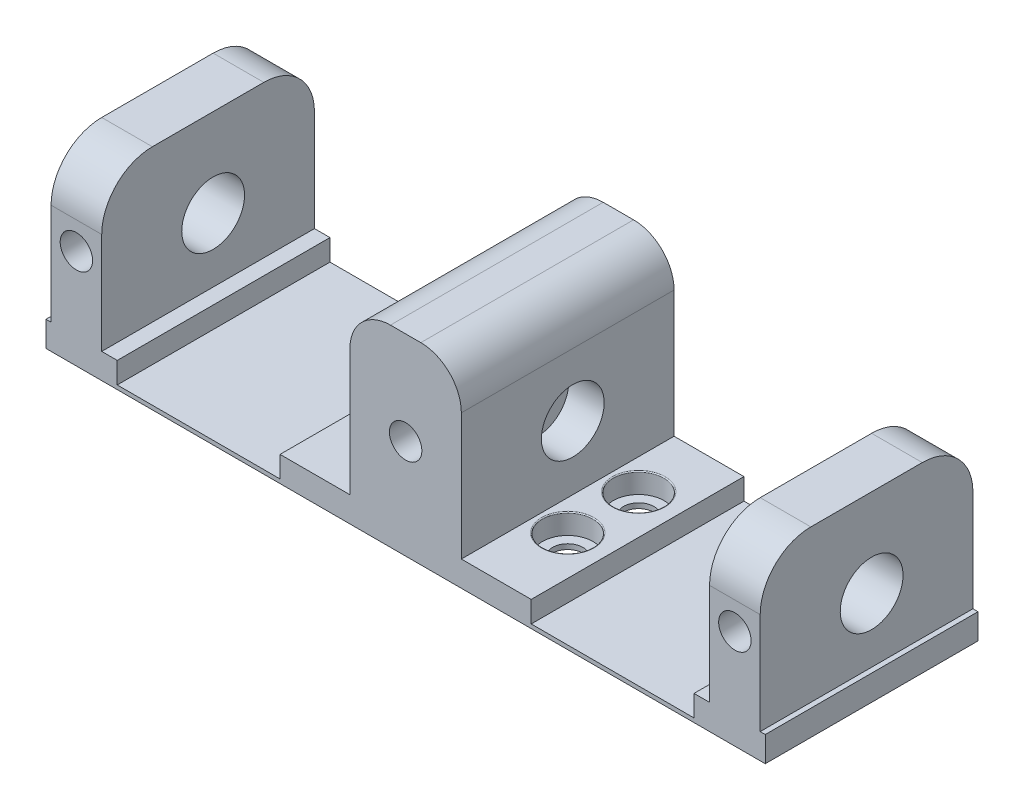
SolidWorks part; units mm, degrees
ref_plane "Alzado" through (0, 0, 0) normal (0, 0, 1) x (1, 0, 0)
ref_plane "Planta" through (0, 0, 0) normal (0, 1, 0) x (1, 0, 0)
ref_plane "Vista lateral" through (0, 0, 0) normal (1, 0, 0) x (0, 0, -1)
sketch "Croquis1" plane through (0, 0, 0) normal (0, 0, 1) x (1, 0, 0)
  line L0 (0, 9.5) -> (0, -9.5) construction
  line L1 (-1.5, 9.5) -> (1.5, 9.5)
  line L2 (-5.5, 5.5) -> (-5.5, -7)
  line L3 (-5.5, -9.5) -> (5.5, -9.5)
  line L4 (5.5, 5.5) -> (5.5, -7)
  line L5 (-5.5, 9.5) -> (5.5, -9.5) construction
  line L6 (-5.5, -9.5) -> (5.5, 9.5) construction
  line L7 (-5.5, -9.5) -> (-11.5, -9.5)
  line L9 (-5.5, -7) -> (-11.5, -7)
  line L10 (-11.5, -9.5) -> (-11.5, -7)
  line L11 (5.5, -7) -> (11.5, -7)
  line L12 (11.5, -9.5) -> (11.5, -7)
  line L13 (5.5, -9.5) -> (11.5, -9.5)
  arc A0 (5.5, 5.5) -> (1.5, 9.5) centre (1.5, 5.5) ccw
  arc A1 (-5.5, 5.5) -> (-1.5, 9.5) centre (-1.5, 5.5) cw
  point P0 (0, 0)
  dimension "D1" = 4
  dimension "D2" = 6
  dimension "D3" = 2.5
  dimension "D4" = 11
  dimension "D5" = 15
extrude "Saliente-Extruir1" add sketch "Croquis1" against normal blind 11 and the other way blind 10
sketch "Croquis2" plane through (5.5, 0, 0) normal (1, 0, 0) x (0, 0, -1)
  line L0 (0.5, 9.5) -> (0.5, -7) construction
  line L1 (11, 9.5) -> (-10, 9.5) construction
  line L2 (11, -7) -> (-10, -7) construction
  line L3 (11, -9.5) -> (-10, -9.5) construction
  line L4 (-10, -7) -> (-10, 5.5) construction
  circle A0 centre (1, -0.68) radius 3.1
  point P10 (0, 0)
  dimension "D2" = 6.2
  dimension "D1" = 8.82
  dimension "D3" = 11
extrude "Cortar-Extruir1" cut sketch "Croquis2" against normal blind 3.5
sketch "Croquis3" plane through (-5.5, 0, 0) normal (-1, 0, 0) x (0, 0, 1)
  line L0 (-0.5, 9.5) -> (-0.5, -7) construction
  line L1 (-11, 9.5) -> (10, 9.5) construction
  line L2 (-11, -7) -> (10, -7) construction
  line L3 (-11, -9.5) -> (10, -9.5) construction
  line L4 (10, 5.5) -> (10, -7) construction
  circle A0 centre (-1, -0.68) radius 3.1
  point P10 (0, 0)
  dimension "D2" = 6.2
  dimension "D1" = 8.82
  dimension "D3" = 11
extrude "Cortar-Extruir2" cut sketch "Croquis3" against normal blind 3.5
sketch "Croquis4" plane through (0, -7, 0) normal (0, 1, 0) x (1, 0, 0)
  line L0 (0, 11) -> (0, 0) construction
  line L1 (1.5, 11) -> (-1.5, 11) construction
  line L2 (-8.5, 11) -> (-8.5, -10) construction
  line L3 (-5.5, 11) -> (-11.5, 11) construction
  line L4 (-5.5, -10) -> (-11.5, -10) construction
  line L7 (-11.5, 11) -> (-11.5, -10) construction
  line L8 (-11.5, 0.5) -> (-8.5, 0.5) construction
  circle A0 centre (-8.5, 4.5) radius 2.5
  circle A1 centre (-8.5, -2.5) radius 2.5
  circle A2 centre (8.5, -2.5) radius 2.5
  circle A3 centre (8.5, 4.5) radius 2.5
  dimension "D1" = 5
  dimension "D2" = 7
  dimension "D3" = 6.5
extrude "Cortar-Extruir3" cut sketch "Croquis4" against normal blind 2
fillet "Redondeo1" radius 0.1 4 edges at (11, -7, 2.5) (11, -7, -4.5) (-11, -7, 2.5) (-11, -7, -4.5)
sketch "Croquis5" plane through (0, -7, 0) normal (0, 1, 0) x (1, 0, 0)
  line L0 (-8.5, 11) -> (-8.5, -10) construction
  line L1 (-5.5, 11) -> (-11.5, 11) construction
  line L2 (-5.5, -10) -> (-11.5, -10) construction
  line L3 (0, 11) -> (0, -10) construction
  line L4 (1.5, 11) -> (-1.5, 11) construction
  line L5 (1.5, -10) -> (-1.5, -10) construction
  circle A0 centre (-8.5, 4.5) radius 1.5
  circle A1 centre (-8.5, -2.5) radius 1.5
  circle A2 centre (-8.5, 4.5) radius 2.6 construction
  circle A3 centre (8.5, -2.5) radius 1.5
  circle A4 centre (8.5, 4.5) radius 1.5
  dimension "D1" = 3
extrude "Cortar-Extruir4" cut sketch "Croquis5" against normal through all
sketch "Croquis6" plane through (-11.5, 0, 0) normal (-1, 0, 0) x (0, 0, 1)
  line L1 (-11, -7) -> (10, -7)
  line L2 (-11, -7) -> (-11, -9.5)
  line L3 (-11, -9.5) -> (10, -9.5)
  line L4 (10, -7) -> (10, -9.5)
extrude "Saliente-Extruir2" add sketch "Croquis6" along normal blind 24
sketch "Croquis7" plane through (11.5, 0, 0) normal (1, 0, 0) x (0, 0, -1)
  line L1 (-10, -7) -> (11, -7)
  line L2 (-10, -7) -> (-10, -9.5)
  line L3 (-10, -9.5) -> (11, -9.5)
  line L4 (11, -7) -> (11, -9.5)
extrude "Saliente-Extruir3" add sketch "Croquis7" along normal blind 24
sketch "Croquis8" plane through (0, -7, 0) normal (0, 1, 0) x (1, 0, 0)
  line L0 (-5.5, 11) -> (-35.5, 11) construction
  line L1 (-35, 11) -> (-30, 11)
  line L2 (-35, 11) -> (-35, -10)
  line L3 (-35, -10) -> (-30, -10)
  line L4 (-30, 11) -> (-30, -10)
  line L5 (-5.5, -10) -> (-35.5, -10) construction
  line L6 (0, 11) -> (0, 0) construction
  line L7 (1.5, 11) -> (-1.5, 11) construction
  line L8 (35, -10) -> (30, -10)
  line L9 (30, 11) -> (30, -10)
  line L10 (35, 11) -> (30, 11)
  line L11 (35, 11) -> (35, -10)
  line L12 (-35.5, -10) -> (-35.5, 11) construction
  dimension "D1" = 5
  dimension "D2" = 0.5
extrude "Saliente-Extruir4" add sketch "Croquis8" along normal blind 15
fillet "Redondeo4" radius 5 2 edges at (-32.5, 8, -11) (-32.5, 8, 10)
fillet "Redondeo5" radius 5 2 edges at (32.5, 8, -11) (32.5, 8, 10)
ref_plane "Plano12" through (0, 0, -0.5) normal (0, 0, 1) x (1, 0, 0)
sketch "Croquis34" plane through (0, 0, 10) normal (0, 0, 1) x (1, 0, 0)
  line L0 (-30, -7) -> (-28.4683, -7)
  line L1 (-5.5, -7) -> (-30, -7) construction
  line L2 (-28.4683, -7) -> (-28.4683, -9.1)
  line L3 (-28.4683, -9.1) -> (-12.3966, -9.1)
  line L4 (-12.3966, -9.1) -> (-12.3966, -7)
  line L5 (-28.4683, -7) -> (-12.3966, -7)
  line L6 (0, -9.5) -> (0, 0) construction
  line L8 (28.4683, -7) -> (28.4683, -9.1)
  line L9 (28.4683, -9.1) -> (12.3966, -9.1)
  line L10 (12.3966, -9.1) -> (12.3966, -7)
  line L11 (28.4683, -7) -> (12.3966, -7)
  point P10 (-28.4683, -7)
  point P11 (0, 0)
  line M23 (-5.5, -7) -> (-30, -7)
  dimension "D3" = 2.1
extrude "Cortar-Extruir7" cut sketch "Croquis34" against normal through all contours L3 L4 L2 M23 | L11 L10 L9 L8 region at (-20.4325, -8.05, 10)
sketch "Croquis35" plane through (0, -9.5, 0) normal (0, -1, 0) x (1, 0, 0)
  line L0 (-31, 10) -> (-31, -11) construction
  line L1 (-35.5, 10) -> (35.5, 10) construction
  line L2 (-35.5, -11) -> (35.5, -11) construction
  line L4 (0, 10) -> (0, -11) construction
  circle A0 centre (-31, 2.5) radius 1.5
  circle A1 centre (-31, -4.5) radius 1.5
  circle A2 centre (31, -4.5) radius 1.5
  circle A3 centre (31, 2.5) radius 1.5
  circle A4 centre (-8.5, 2.5) radius 1.5 construction
  circle A5 centre (-8.5, 2.5) radius 1.5
  point P21 (0, 0)
  dimension "D2" = 3
  dimension "D3" = 7
  dimension "D1" = 22.5
extrude "Cortar-Extruir8" cut sketch "Croquis35" against normal blind 2.2
sketch "Croquis36" plane through (0, 0, 10) normal (0, 0, 1) x (1, 0, 0)
  line L0 (-32.5, 3) -> (-32.5, -9.5) construction
  line L1 (-30, 3) -> (-35, 3) construction
  line L2 (-35.5, -9.5) -> (35.5, -9.5) construction
  line L3 (0, 9.5) -> (0, -9.5) construction
  line L4 (1.5, 9.5) -> (-1.5, 9.5) construction
  line L5 (32.5, 3) -> (32.5, -9.5) construction
  line L6 (35, 3) -> (30, 3) construction
  circle A0 centre (-32.5, 0.3126) radius 1.6
  circle A1 centre (32.5, 0.3126) radius 1.6
  circle A2 centre (0, 0.3126) radius 1.6
  point P21 (0, 0)
  dimension "D1" = 3.2
  dimension "D2" = 3.2
extrude "Cortar-Extruir9" cut sketch "Croquis36" against normal blind 4.5 contours A0 | A2 | A1
sketch "Croquis37" plane through (35, 0, 0) normal (1, 0, 0) x (0, 0, -1)
  line L0 (7.6864, -9.5) -> (-5.5802, 8) construction
  line L1 (-10, -9.5) -> (11, -9.5) construction
  line L2 (-5, 8) -> (6, 8) construction
  line L3 (-10, 3) -> (-10, -7) construction
  circle A0 centre (1, -0.68) radius 3.1
  point P8 (0, 0)
  dimension "D2" = 6.2
  dimension "D1" = 8.82
  dimension "D3" = 11
extrude "Cortar-Extruir10" cut sketch "Croquis37" against normal blind 7
sketch "Croquis38" plane through (-35, 0, 0) normal (-1, 0, 0) x (0, 0, 1)
  line L0 (-1, -9.5) -> (-1, 8) construction
  line L1 (-11, -9.5) -> (10, -9.5) construction
  line L2 (-6, 8) -> (5, 8) construction
  line L3 (10, 3) -> (10, -7) construction
  circle A0 centre (-1, -0.68) radius 3.1
  dimension "D1" = 6.2
  dimension "D2" = 8.82
  dimension "D3" = 11
extrude "Cortar-Extruir11" cut sketch "Croquis38" against normal blind 7
